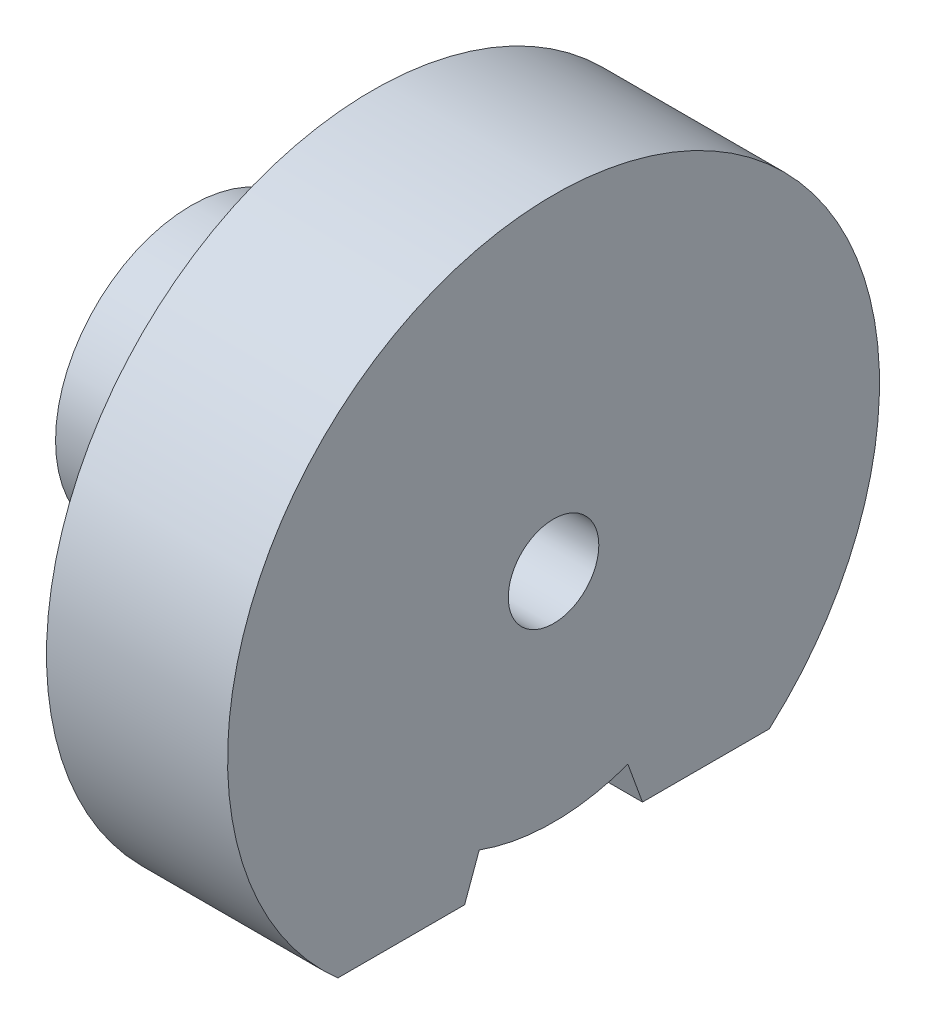
SolidWorks part; units mm, degrees
ref_plane "Plan de face" through (0, 0, 0) normal (0, 0, 1) x (1, 0, 0)
ref_plane "Plan de dessus" through (0, 0, 0) normal (0, 1, 0) x (1, 0, 0)
ref_plane "Plan de droite" through (0, 0, 0) normal (1, 0, 0) x (0, 0, -1)
sketch "Esquisse29" plane through (0, 0, 0) normal (0, 0, 1) x (1, 0, 0)
  line L0 (-2, 0) -> (-5, 0)
  line L1 (5, 0) -> (2, 0)
  line L2 (5, 0) -> (5, -12)
  line L3 (5, -12) -> (-5, -12)
  line L4 (-5, 0) -> (-5, -12)
  line L5 (0, 0) -> (0, -2) construction
  line L6 (-5, 0) -> (5, 0)
  line L7 (-5, 0) -> (-5, 6)
  line L8 (5, 0) -> (5, 6)
  line L9 (-5, 6) -> (5, 6)
  arc A0 (-2, 0) -> (2, 0) centre (0, 0) ccw
  circle A1 centre (0, 0) radius 2
  dimension "D1" = 4
  dimension "D2" = 10
  dimension "D3" = 12
  dimension "D4" = 18
revolve "Révolution2" add sketch "Esquisse29" angle 360 about L3 region at (0, -6.2846, 0)
revolve "Révolution3" add sketch "Esquisse29<3>" angle 320 mid plane about L3 region at (0, 3.2516, 0)
sketch "Esquisse29<3>" plane through (0, 0, 0) normal (0, 0, 1) x (1, 0, 0) same geometry as "Esquisse29"
chamfer "Chanfrein1" distance 10 angle 20 1 edges at (0, -28.9145, -6.1564) first distance on face at (0, -11.4572, 0)
chamfer "Chanfrein3" distance 10 angle 20 1 edges at (0, -28.9145, 6.1564) first distance on face at (0, -10.7592, 0.2349)
sketch "Esquisse30" plane through (5, 0, 0) normal (1, 0, 0) x (0, 0, -1)
  circle A0 centre (0, -12) radius 2.5
  dimension "D1" = 5
extrude "Enlèv. mat.-Extru.1" cut sketch "Esquisse30" against normal blind 10
sketch "Esquisse31" plane through (-5, 0, 0) normal (-1, 0, 0) x (0, 0, 1)
  circle A0 centre (0, -12) radius 7.5
  circle A1 centre (0, -12) radius 2.5 construction
  circle A2 centre (0, -12) radius 2.5
  dimension "D1" = 15
extrude "Boss.-Extru.1" add sketch "Esquisse31" along normal blind 10
sketch "Esquisse32" plane through (0, 0, 0) normal (0, 0, 1) x (1, 0, 0)
  line L0 (-5, -4.5) -> (-5, -19.5) construction
  line L1 (-15, -4.5) -> (-15, -19.5) construction
  line L2 (-5, -4.5) -> (-5, -19.5)
  line L3 (-15, -4.5) -> (-15, -19.5)
  line L4 (-15, -12) -> (-5, -12) construction
  circle A0 centre (-10, -12) radius 1.2313
  dimension "D1" = 2.4626
extrude "Enlèv. mat.-Extru.2" cut sketch "Esquisse32" against normal blind 10 contours A0
fillet "Congé1" radius 2 1 edges at (-5, -12, 7.5)
ref_axis "Axe1" through (-15, -12, 0) along (1, 0, 0)
